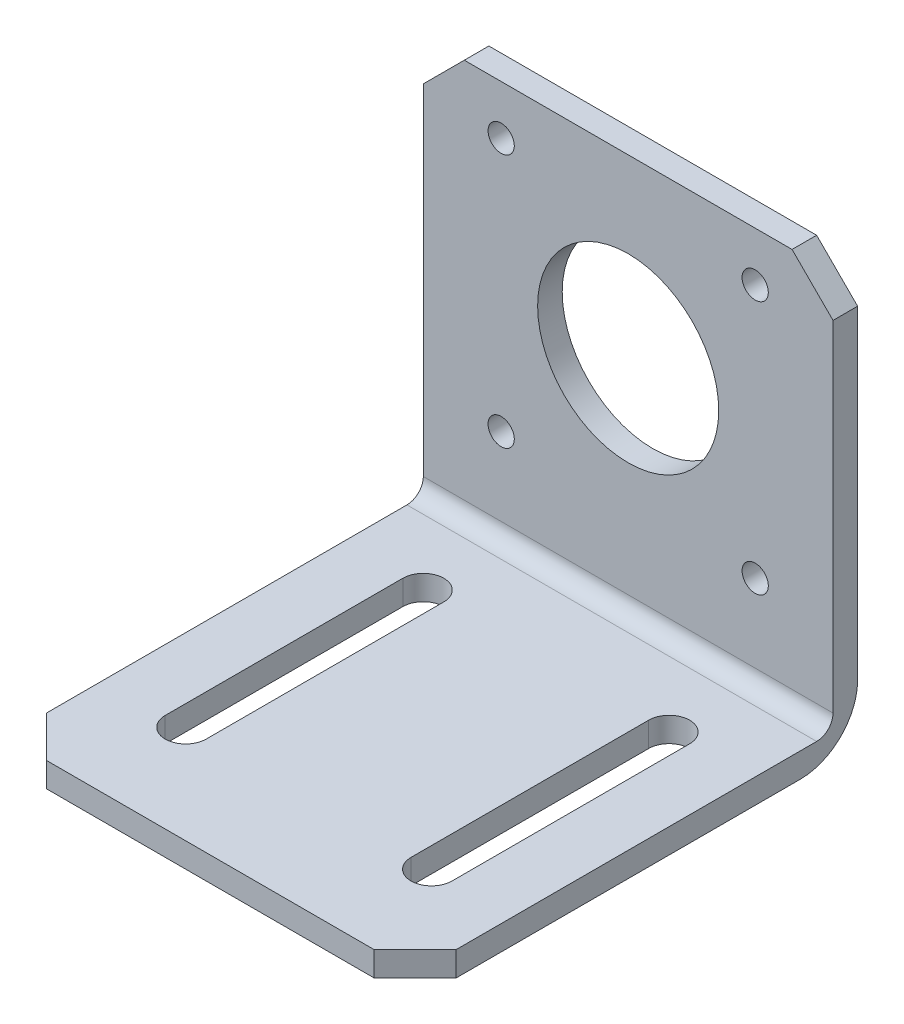
SolidWorks part; units mm, degrees
material "Plain Carbon Steel"
ref_plane "Front Plane" through (0, 0, 0) normal (0, 0, 1) x (1, 0, 0)
ref_plane "Top Plane" through (0, 0, 0) normal (0, 1, 0) x (1, 0, 0)
ref_plane "Right Plane" through (0, 0, 0) normal (1, 0, 0) x (0, 0, -1)
sketch "Sketch1" plane through (0, 0, 0) normal (0, 0, 1) x (1, 0, 0)
  line L1 (0, 0) -> (50, 0)
  line L2 (0, 0) -> (0, 51.5)
  line L3 (0, 51.5) -> (50, 51.5)
  line L4 (50, 0) -> (50, 51.5)
  dimension "D1" = 50
  dimension "D2" = 51.5
extrude "Boss-Extrude1" add sketch "Sketch1" along normal blind 3
sketch "Sketch2" plane through (0, 0, 3) normal (0, 0, 1) x (1, 0, 0)
  line L0 (50, 0) -> (50, 51.5) construction
  line L1 (0, 0) -> (50, 0)
  line L2 (0, 0) -> (0, 3)
  line L3 (0, 3) -> (50, 3)
  line L4 (50, 0) -> (50, 3)
  dimension "D1" = 3
extrude "Boss-Extrude2" add sketch "Sketch2" along normal blind 51
sketch "Sketch3" plane through (0, 0, 0) normal (0, 0, -1) x (-1, 0, 0)
  line L0 (-40.5, 45.5) -> (-40.5, 14.5) construction
  line L1 (-40.5, 14.5) -> (-9.5, 14.5) construction
  line L2 (-9.5, 14.5) -> (-9.5, 45.5) construction
  line L3 (-9.5, 45.5) -> (-40.5, 45.5) construction
  line L4 (-40.5, 45.5) -> (-9.5, 14.5) construction
  line L7 (-50, 0) -> (-50, 51.5) construction
  line L8 (27.5, 0) -> (-27.5, 0) construction
  circle A0 centre (-25, 30) radius 11.05
  circle A1 centre (-40.5, 45.5) radius 1.6
  circle A2 centre (-9.5, 45.5) radius 1.6
  circle A3 centre (-9.5, 14.5) radius 1.6
  circle A4 centre (-40.5, 14.5) radius 1.6
  point P2 (-40.1941, 44.9832)
  point P3 (0, 0)
  point P5 (-38.8126, 46.6898)
  dimension "D1" = 31
  dimension "D4" = 3.2
  dimension "D5" = 3.2
  dimension "D6" = 3.2
  dimension "D7" = 3.2
  dimension "D2" = 25
  dimension "D3" = 30
extrude "Cut-Extrude1" cut sketch "Sketch3" against normal through all
sketch "Sketch4" plane through (0, 3, 0) normal (0, 1, 0) x (1, 0, 0)
  line L0 (10, -13) -> (10, -42) construction
  line L1 (12.5, -13) -> (12.5, -42)
  line L2 (7.5, -13) -> (7.5, -42)
  line L3 (40, -42) -> (40, -13) construction
  line L4 (37.5, -42) -> (37.5, -13)
  line L5 (42.5, -42) -> (42.5, -13)
  line L6 (50, -3) -> (0, -3) construction
  line L7 (50, -3) -> (0, -3) construction
  line L8 (12.5, -13) -> (37.5, -42) construction
  line L9 (0, -28.325) -> (0, 28.325) construction
  arc A0 (12.5, -13) -> (7.5, -13) centre (10, -13) ccw
  arc A1 (7.5, -42) -> (12.5, -42) centre (10, -42) ccw
  arc A2 (37.5, -42) -> (42.5, -42) centre (40, -42) ccw
  arc A3 (42.5, -13) -> (37.5, -13) centre (40, -13) ccw
  point P2 (10, -27.5)
  point P7 (40, -27.5)
  point P14 (10, -10.5)
  point P15 (10, -44.5)
  point P16 (40, -10.5)
  point P17 (40, -44.5)
  point P24 (25, -27.5)
  dimension "D1" = 34
  dimension "D2" = 34
  dimension "D3" = 7.5
  dimension "D4" = 7.5
  dimension "D5" = 25
  dimension "D6" = 5
  dimension "D7" = 5
  dimension "D8" = 25
extrude "Cut-Extrude2" cut sketch "Sketch4" against normal through all
chamfer "Chamfer1" distance 5 4 edges at (0, 1.5, 54) (50, 1.5, 54) (0, 51.5, 1.5) (50, 51.5, 1.5)
fillet "Fillet1" radius 7 1 edges at (25, 0, 0)
fillet "Fillet2" radius 2 1 edges at (25, 3, 3)
ref_axis "Axis1" through (25, 30, 3) along (0, 0, -1)
ref_plane "Plane1" through (25, 0, 0) normal (1, 0, 0) x (0, 0, -1)
